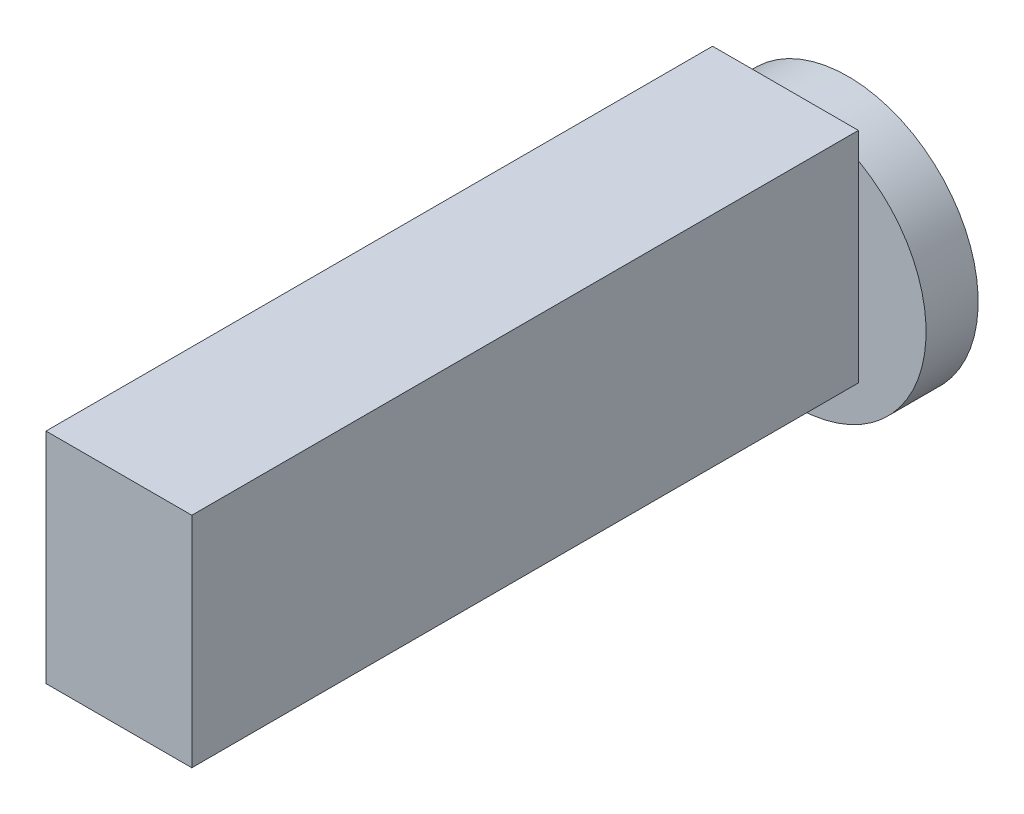
SolidWorks part; units mm, degrees
note: The reader was unsure of these and kept them because the rebuilt part matched: shared geometry of "Sketch19<2>", "Sketch23<3>".
ref_plane "Front Plane" through (0, 0, 0) normal (0, 0, 1) x (1, 0, 0)
ref_plane "Top Plane" through (0, 0, 0) normal (0, 1, 0) x (1, 0, 0)
ref_plane "Right Plane" through (0, 0, 0) normal (1, 0, 0) x (0, 0, -1)
sketch "Sketch1" plane through (0, 0, 0) normal (0, 0, 1) x (1, 0, 0)
  circle A0 centre (0, 0) radius 5
extrude "Body" add sketch "Sketch1" against normal blind 100
ref_plane "Plane1" through (0, 0, -100) normal (0, 0, -1) x (-1, 0, 0)
sketch "Sketch2" plane through (0, 0, -100) normal (0, 0, -1) x (-1, 0, 0)
  circle A0 centre (0, 0) radius 25
extrude "Head" add sketch "Sketch2" along normal blind 10 contours A0
sketch "Sketch10" plane through (0, 0, 0) normal (0, 0, 1) x (1, 0, 0)
  circle A0 centre (0, 0) radius 7.5
curve "Threads" pitch 28.5 height 105 turns 3.6842
ref_plane "Plane2" through (-7.5, 0, 0) normal (0, 0.8557, -0.5175) x (1, 0, 0)
sketch "Sketch17" plane through (-7.5, 0, 0) normal (0, 0.8557, -0.5175) x (1, 0, 0)
  line L1 (-2.9168, -0.1382) -> (3.0832, -3.6023)
  line L2 (3.0832, -3.6023) -> (3.0832, 3.3259)
  line L3 (3.0832, 3.3259) -> (-2.9168, -0.1382)
  circle A0 centre (1.0832, -0.1382) radius 2 construction
sweep "Sweep1" add profiles "Sketch17" path "Threads"
sketch "Sketch18" plane through (0, 0, 0) normal (0, 0, 1) x (1, 0, 0)
  circle A0 centre (0, 0) radius 14.102
extrude "Cut-Extrude1" cut sketch "Sketch18" along normal blind 17
ref_plane "Plane3" through (0, 0, 30) normal (0, 0, 1) x (1, 0, 0)
sketch "Sketch19" plane through (0, 0, 30) normal (0, 0, 1) x (1, 0, 0)
  line L1 (12, 27) -> (-12, 27)
  line L2 (12, 27) -> (12, -11)
  line L3 (12, -11) -> (-12, -11)
  line L4 (-12, 27) -> (-12, -11)
  point P0 (0, 0)
extrude "Frame" add sketch "Sketch19" against normal blind 128 thin
extrude "Boss-Extrude3" add sketch "Sketch19<2>" against normal blind 2
sketch "Sketch19<2>" plane through (0, 0, 30) normal (0, 0, 1) x (1, 0, 0) same geometry as "Sketch19"
ref_plane "Plane5" through (0, -11, 0) normal (0, 1, 0) x (1, 0, 0)
sketch "Sketch23" plane through (0, -11, 0) normal (0, 1, 0) x (1, 0, 0)
  line L0 (-12, 98) -> (-12, -28) construction
  line L1 (12, -28) -> (-12, -28)
  line L2 (12, -28) -> (12, 0)
  line L3 (12, 0) -> (-12, 0)
  line L4 (-12, -28) -> (-12, 0)
extrude "Hole" add sketch "Sketch23" against normal blind 2
extrude "Cut-Extrude2" cut sketch "Sketch23<3>" against normal blind 2
sketch "Sketch23<3>" plane through (0, -11, 0) normal (0, 1, 0) x (1, 0, 0) same geometry as "Sketch23"
